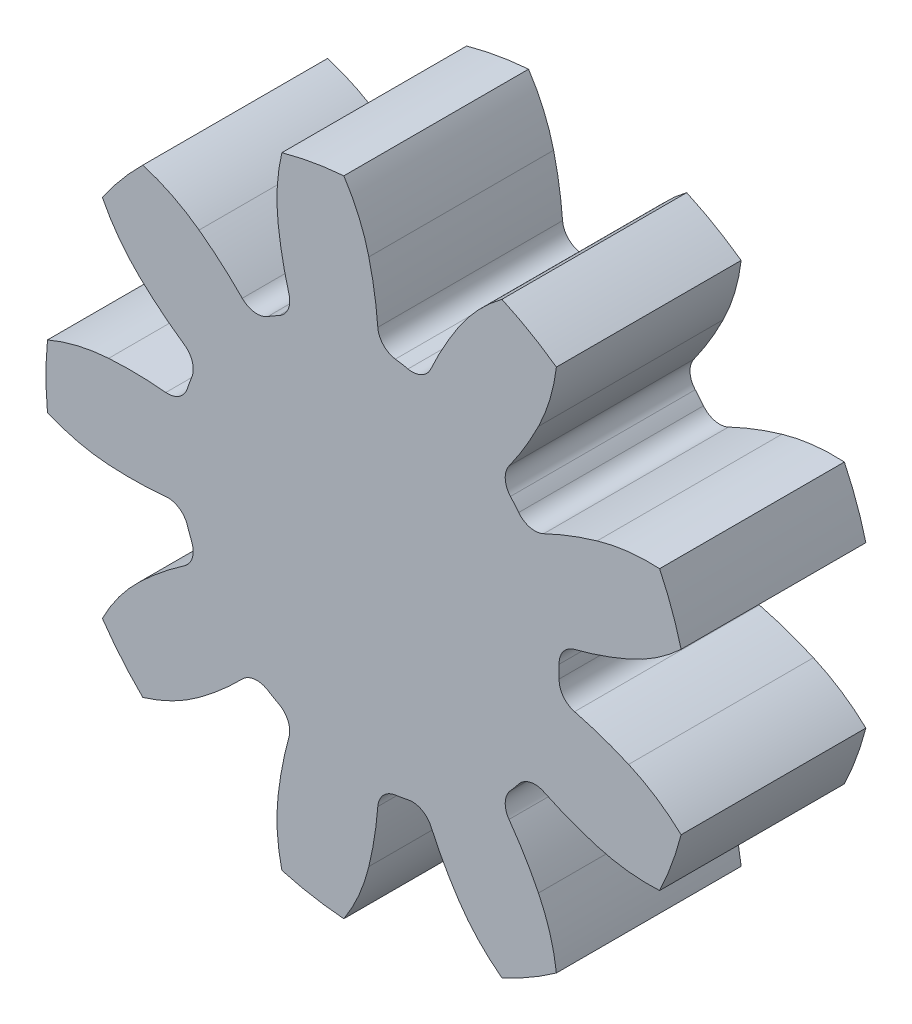
SolidWorks part; units mm, degrees
material "Plain Carbon Steel"
ref_plane "Front" through (0, 0, 0) normal (0, 0, 1) x (1, 0, 0)
ref_plane "Top" through (0, 0, 0) normal (0, 1, 0) x (1, 0, 0)
ref_plane "Right" through (0, 0, 0) normal (1, 0, 0) x (0, 0, -1)
sketch "Sketch1" plane through (0, 0, 0) normal (0, 0, 1) x (1, 0, 0)
  line L0 (0, 0) -> (5.715, 0) construction
  line L1 (5.715, 0) -> (6.985, 0) construction
  circle A0 centre (0, 0) radius 5.715 construction
  circle A1 centre (0, 0) radius 6.985
  dimension "pitch_diameter" = 11.43
  dimension "addendum" = 1.27
extrude "BLANK DISK" add sketch "Sketch1" along normal mid plane 4
sketch "Sketch2" plane through (0, 0, 2) normal (0, 0, 1) x (1, 0, 0)
  line L0 (0, 0) -> (4.1275, 0) construction
  line L1 (4.1275, 0) -> (5.715, 0) construction
  line L2 (0, 0) -> (-6.985, 0) construction
  line L3 (0, 0) -> (-5.3508, -4.4899) construction
  line L4 (-5.763, -3.9469) -> (-4.952, -2.8529) construction
  line L5 (-4.952, -2.8529) -> (-3.6958, -1.8377) construction
  line L6 (-6.9517, -0.6809) -> (-5.6273, -0.9976) construction
  line L7 (-5.6273, -0.9976) -> (-4.0124, -0.9679) construction
  line L8 (-4.3107, -3.6171) -> (-4.952, -2.8529) construction
  line L9 (-5.6273, -0.9976) -> (-5.6273, 0) construction
  line L12 (0, 0) -> (-5.6273, -0.9976) construction
  line L13 (0, 0) -> (-4.952, -2.8529) construction
  line L14 (-4.952, -2.8529) -> (-2.9471, -6.3328) construction
  line L15 (-5.6273, -0.9976) -> (-6.3283, 2.9568) construction
  line L16 (-4.952, -2.8529) -> (-5.6273, -0.9976) construction
  line L17 (-3.8786, -1.4117) -> (-4.0124, -0.9679) construction
  line L18 (-3.8786, -1.4117) -> (-3.6958, -1.8377) construction
  circle A0 centre (0, 0) radius 5.715 construction
  circle A1 centre (0, 0) radius 4.1275 construction
  circle A2 centre (0, 0) radius 6.985 construction
  arc A3 (-5.763, -3.9469) -> (-6.9517, -0.6809) centre (0, 0) cw
  arc A4 (-3.6958, -1.8377) -> (-4.0124, -0.9679) centre (0, 0) cw construction
  arc A6 (-5.763, -3.9469) -> (-4.952, -2.8529) centre (-2.199, -5.7416) cw
  arc A7 (-6.9517, -0.6809) -> (-5.6273, -0.9976) centre (-5.3752, 2.9848) ccw
  arc A8 (-4.952, -2.8529) -> (-3.9902, -2.0738) centre (0.3598, -8.4265) cw
  arc A9 (-5.6273, -0.9976) -> (-4.3897, -0.9762) centre (-5.1408, 6.6864) ccw
  arc A10 (-3.9902, -2.0738) -> (-3.829, -1.5411) centre (-4.2414, -1.707) ccw
  arc A11 (-4.3897, -0.9762) -> (-3.9238, -1.2807) centre (-4.3463, -1.4186) cw
  arc A12 (-3.829, -1.5411) -> (-3.9238, -1.2807) centre (0, 0) cw
  dimension "D12" = 3.9903
  dimension "D3" = 40
  dimension "D4" = 0.9976
  dimension "D5" = 0.9976
  dimension "D11" = 1.9744
  dimension "D14" = 9
  dimension "D15" = 9
  dimension "base_fillet" = 0.4445
  dimension "pitch_diameter" = 11.43
  dimension "deddendum" = 1.5875
extrude "GEAR TOOTH CUT" cut sketch "Sketch2" against normal through all
ref_axis "CENTER AXIS" through (0, 0, 50) along (0, 0, -1)
pattern_circular "GEAR TEETH REVOLVE" count 9 over 360 about axis through (0, 0, 50) along (0, 0, -1) of "GEAR TOOTH CUT"
sketch "Sketch4" plane through (0, 0, 2) normal (0, 0, 1) x (1, 0, 0)
  circle A0 centre (0, 0) radius 6.35
  dimension "D1" = 12.7
extrude "Extrude1" [suppressed] add sketch "Sketch4" along normal blind 0.635
sketch "Sketch3" plane through (0, 0, 2) normal (0, 0, 1) x (1, 0, 0)
  line L1 (2.9524, 4.6395) -> (-2.5417, 4.8766)
  line L2 (-2.5417, 4.8766) -> (-5.4941, 0.2371)
  line L3 (-5.4941, 0.2371) -> (-2.9524, -4.6395)
  line L4 (-2.9524, -4.6395) -> (2.5417, -4.8766)
  line L5 (2.5417, -4.8766) -> (5.4941, -0.2371)
  line L6 (5.4941, -0.2371) -> (2.9524, 4.6395)
  circle A0 centre (0, 0) radius 4.7625 construction
  dimension "HEX_SIZE" = 9.525
extrude "HEX BORE CUT" [suppressed] cut sketch "Sketch3" against normal through all and the other way through all
equation "\"N_teeth\"= 9.000000"
equation "\"pitch_diameter\"= .45000000"
equation "\"Pd\"=\"N_teeth\"/\"pitch_diameter\""
equation "\"addendum\"=1.000/\"Pd\""
equation "\"face_width\"= 4mm"
equation "\"deddendum\"=1.250/\"Pd\""
equation "\"D3@Sketch2\" = 360/\"N_teeth\""
equation "\"tooth_thickness\"=1.571/\"Pd\""
equation "\"D4@Sketch2\" = \"tooth_thickness\"/2"
equation "\"D5@Sketch2\" = \"tooth_thickness\"/2"
equation "\"Pressure_Angle\"=14.500000"
equation "\"base_fillet\"=0.35/\"Pd\""
equation "\"D12@Sketch2\" = 2*\"tooth_thickness\""
equation "\"hub_diameter\"= 0.300000"
equation "\"bore\"= 0.125000"
equation "\"hub_projection\"=0.250000"
equation "\"sss_diam\"=0.062500"
